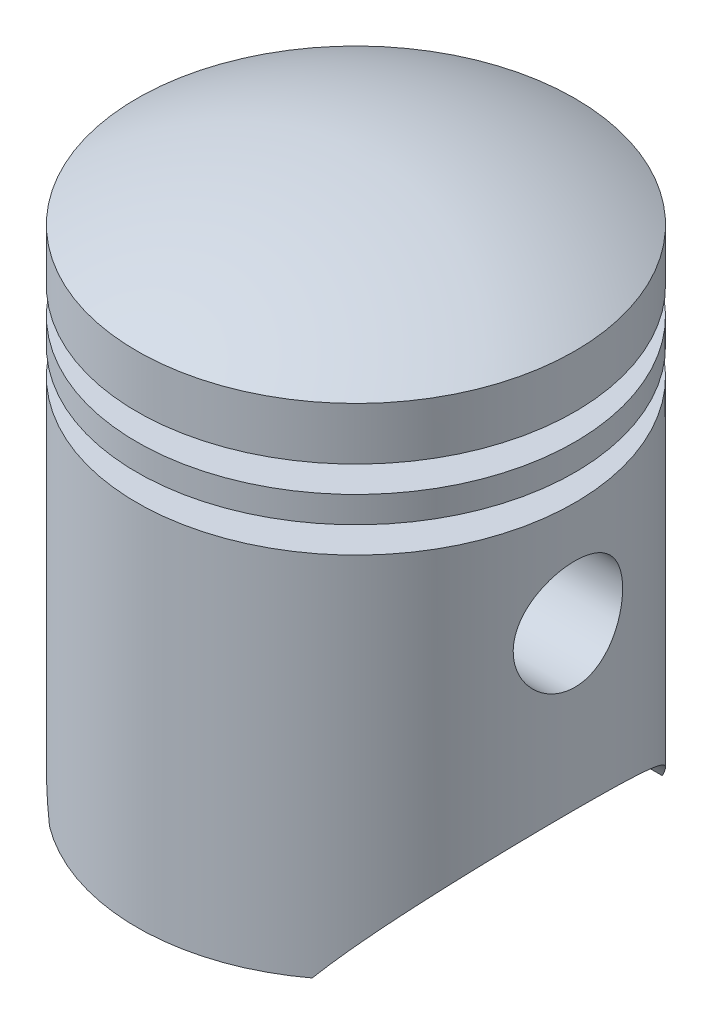
SolidWorks part; units mm, degrees
ref_plane "前视基准面" through (0, 0, 0) normal (0, 0, 1) x (1, 0, 0)
ref_plane "上视基准面" through (0, 0, 0) normal (0, 1, 0) x (1, 0, 0)
ref_plane "右视基准面" through (0, 0, 0) normal (1, 0, 0) x (0, 0, -1)
sketch "草图2" plane through (0, 0, 0) normal (0, 0, 1) x (1, 0, 0)
  line L0 (0, 0) -> (0, 86.1951) construction
  line L1 (0, 57) -> (25, 57) construction
  line L2 (25, 57) -> (25, 51)
  line L3 (25, 51) -> (20, 51)
  line L4 (20, 51) -> (20, 48)
  line L5 (20, 48) -> (25, 48)
  line L6 (25, 48) -> (25, 45)
  line L7 (25, 45) -> (20, 45)
  line L8 (20, 45) -> (20, 42)
  line L9 (20, 42) -> (25, 42)
  line L10 (25, 42) -> (25, 0)
  line L11 (25, 0) -> (0, 0)
  line L12 (0, 63.5478) -> (0, 0)
  arc A0 (25, 57) -> (0, 63.5478) centre (0, 12.5478) ccw
  arc A1 (0, 63.5478) -> (25, 57) centre (0, 12.5478) ccw construction
  dimension "D6" = 102
  dimension "D1" = 25
  dimension "D2" = 42
  dimension "D3" = 3
  dimension "D4" = 6
  dimension "D5" = 20
revolve "旋转1" add sketch "草图2" angle 360 about L0
sketch "草图3" plane through (0, 0, 0) normal (1, 0, 0) x (0, 0, -1)
  line L0 (0, 0) -> (0, 63.5478) construction
  line L1 (-25, 0) -> (25, 0) construction
  line L2 (-20, 0) -> (20, 0)
  arc A0 (25, 57) -> (-25, 57) centre (0, 12.5478) ccw construction
  circle A1 centre (0, 30) radius 6.25
  circle A2 centre (0, -11.3578) radius 23
  point P12 (0, 0)
  dimension "D1" = 12.5
  dimension "D4" = 46
  dimension "D2" = 30
  dimension "D3" = 40
extrude "切除-拉伸1" cut sketch "草图3" against normal mid plane 100 contours A1
shell "抽壳5" thickness 2 removed face at (0, 0, -25)
sketch "草图5" plane through (0, 0, 0) normal (0, -1, 0) x (1, 0, 0)
  line L1 (10, -10) -> (-10, -10)
  line L2 (10, -10) -> (10, 10)
  line L3 (10, 10) -> (-10, 10)
  line L4 (-10, -10) -> (-10, 10)
  line L5 (10, -10) -> (-10, 10) construction
  line L6 (10, 10) -> (-10, -10) construction
  point P0 (0, 0)
  dimension "D1" = 20
extrude "切除-拉伸3" cut sketch "草图5" against normal blind 45
extrude "切除-拉伸4" cut sketch "草图3<4>" against normal blind 45 and the other way blind 45 contours A2
sketch "草图3<4>" plane through (0, 0, 0) normal (1, 0, 0) x (0, 0, -1) same geometry as "草图3"
